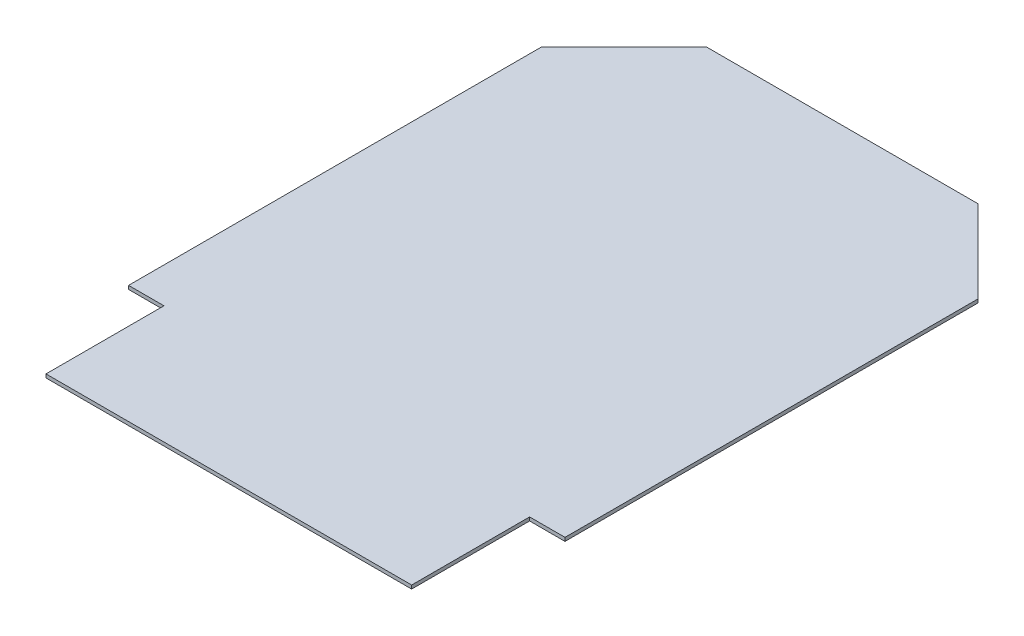
SolidWorks part; units mm, degrees
ref_plane "Front Plane" through (0, 0, 0) normal (0, 0, 1) x (1, 0, 0)
ref_plane "Top Plane" through (0, 0, 0) normal (0, 1, 0) x (1, 0, 0)
ref_plane "Right Plane" through (0, 0, 0) normal (1, 0, 0) x (0, 0, -1)
sketch "BaseSketch" plane through (0, 0, 0) normal (0, 1, 0) x (1, 0, 0)
  line L0 (140.97, 317.5) -> (222.25, 236.22) construction
  line L1 (-171.45, -317.5) -> (171.45, -317.5)
  line L2 (-222.25, -190.5) -> (-222.25, 317.5)
  line L3 (-222.25, 317.5) -> (222.25, 317.5)
  line L4 (222.25, -190.5) -> (222.25, 317.5)
  line L5 (-222.25, -317.5) -> (222.25, 317.5) construction
  line L6 (-222.25, 317.5) -> (222.25, -317.5) construction
  line L7 (222.25, -190.5) -> (171.45, -190.5)
  line L8 (171.45, -190.5) -> (171.45, -317.5)
  line L9 (171.45, -317.5) -> (-171.45, -317.5)
  line L10 (-171.45, -317.5) -> (-171.45, -190.5)
  line L11 (-171.45, -190.5) -> (-222.25, -190.5)
  line L12 (222.25, -190.5) -> (222.25, -317.5) construction
  line L13 (222.25, -317.5) -> (171.45, -317.5) construction
  line L14 (-171.45, -317.5) -> (-222.25, -317.5) construction
  line L15 (-222.25, -317.5) -> (-222.25, -190.5) construction
  line L16 (-222.25, 236.22) -> (-140.97, 317.5) construction
  line L17 (0, -2.0955) -> (0, 2.0955) construction
  point P0 (0, 0)
  dimension "D1" = 90
extrude "Boss-Extrude1" add sketch "BaseSketch" along normal blind 3.81 contours L11 L10 L1 L8 L7 L4 L3 L2 region at (0, 0, -12.1677)
sketch "Sketch7" plane through (0, 3.81, 0) normal (0, 1, 0) x (1, 0, 0)
  line L0 (-234.95, -203.2) -> (-196.85, -203.2)
  line L1 (-222.25, 317.5) -> (222.25, 317.5) construction
  line L2 (-222.25, -190.5) -> (-222.25, 317.5) construction
  line L3 (-171.45, -317.5) -> (171.45, -317.5) construction
  line L4 (222.25, -190.5) -> (222.25, 317.5) construction
  line L5 (-196.85, -203.2) -> (-196.85, -330.2)
  line L6 (-234.95, -203.2) -> (-234.95, -330.2) construction
  line L7 (-234.95, -330.2) -> (-196.85, -330.2) construction
  line L8 (196.85, -330.2) -> (196.85, -203.2)
  line L9 (196.85, -203.2) -> (234.95, -203.2)
  line L10 (234.95, -203.2) -> (234.95, -330.2) construction
  line L11 (234.95, -330.2) -> (196.85, -330.2) construction
  line L12 (234.95, -203.2) -> (234.95, 330.2)
  line L13 (234.95, 330.2) -> (-234.95, 330.2)
  line L14 (-234.95, 330.2) -> (-234.95, -203.2)
  line L15 (-196.85, -330.2) -> (196.85, -330.2)
  line L16 (-171.45, -190.5) -> (-222.25, -190.5) construction
  line L17 (-171.45, -317.5) -> (-171.45, -190.5) construction
  point P20 (-196.85, -190.5)
  dimension "D1" = 12.7
  dimension "D2" = 12.7
  dimension "D3" = 12.7
  dimension "D4" = 12.7
  dimension "D5" = 12.7
  dimension "D6" = 25.4
extrude "Boss-Extrude2" add sketch "Sketch7" against normal up to surface (3.81 mm away) up to face at (0, 0, 95.25)
sketch "Sketch8" plane through (0, 3.81, 0) normal (0, 1, 0) x (1, 0, 0)
  line L0 (-234.95, 330.2) -> (-234.95, 241.4805)
  line L1 (-234.95, 330.2) -> (-234.95, -203.2) construction
  line L2 (-234.95, 241.4805) -> (-146.2305, 330.2)
  line L3 (234.95, 330.2) -> (-234.95, 330.2) construction
  line L4 (-146.2305, 330.2) -> (-234.95, 330.2)
  line L5 (146.2305, 330.2) -> (234.95, 241.4805)
  line L6 (234.95, -203.2) -> (234.95, 330.2) construction
  line L7 (234.95, 241.4805) -> (234.95, 330.2)
  line L8 (234.95, 330.2) -> (146.2305, 330.2)
  line L9 (-222.25, 236.22) -> (-140.97, 317.5) construction
  line L10 (140.97, 317.5) -> (222.25, 236.22) construction
  dimension "D1" = 12.7
  dimension "D2" = 12.7
extrude "Cut-Extrude1" cut sketch "Sketch8" against normal through all
